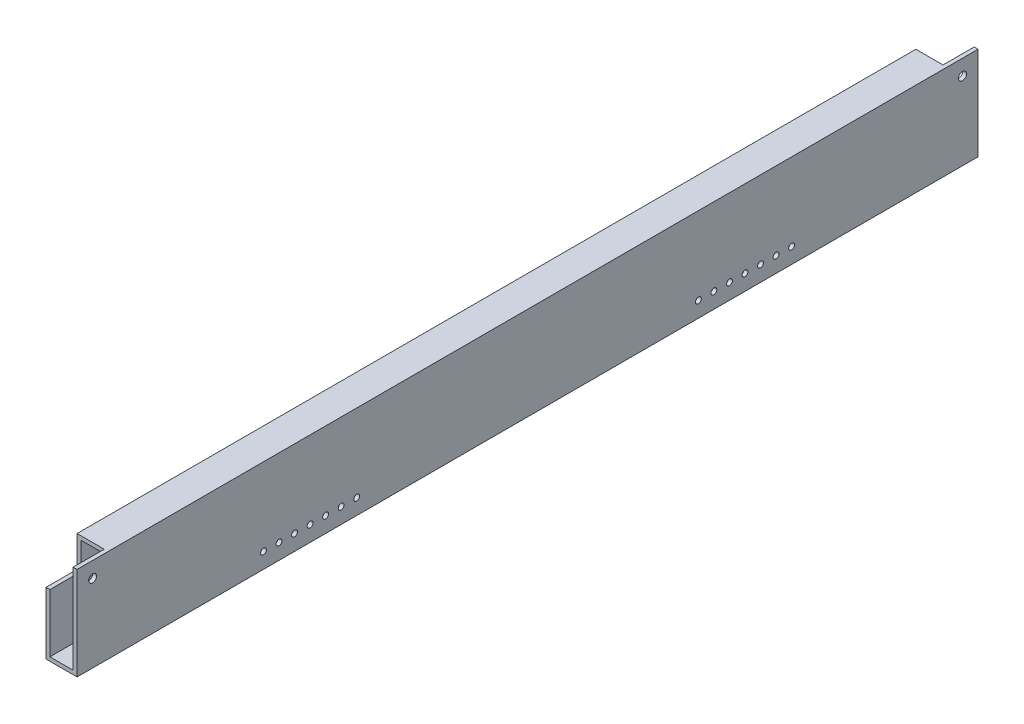
SolidWorks part; units mm, degrees
ref_plane "Front Plane" through (0, 0, 0) normal (0, 0, 1) x (1, 0, 0)
ref_plane "Top Plane" through (0, 0, 0) normal (0, 1, 0) x (1, 0, 0)
ref_plane "Right Plane" through (0, 0, 0) normal (1, 0, 0) x (0, 0, -1)
sketch "Sketch1" plane through (0, 0, 0) normal (0, 0, 1) x (1, 0, 0)
  line L1 (-12.7, -38.1) -> (12.7, -38.1)
  line L2 (-12.7, -38.1) -> (-12.7, 38.1)
  line L3 (-12.7, 38.1) -> (12.7, 38.1)
  line L4 (12.7, -38.1) -> (12.7, 38.1)
  line L5 (-12.7, -38.1) -> (12.7, 38.1) construction
  line L6 (-12.7, 38.1) -> (12.7, -38.1) construction
  point P0 (0, 0)
  dimension "D1" = 25.4
  dimension "D2" = 76.2
extrude "Boss-Extrude1" add sketch "Sketch1" along normal mid plane 736.6
shell "Shell1" thickness 3.175 removed face at (0, 0, -368.3) removed face at (0, 0, 368.3)
sketch "Sketch3" plane through (12.7, 0, 0) normal (1, 0, 0) x (0, 0, -1)
  line L0 (368.3, -38.1) -> (368.3, 38.1) construction
  line L1 (-368.3, -38.1) -> (368.3, -38.1) construction
  line L2 (0, -53.276) -> (0, 47.534) construction
  circle A0 centre (215.9, -25.4) radius 2.3813
  circle A1 centre (203.2, -25.4) radius 2.3813
  circle A2 centre (190.5, -25.4) radius 2.3813
  circle A3 centre (177.8, -25.4) radius 2.3813
  circle A4 centre (165.1, -25.4) radius 2.3813
  circle A5 centre (152.4, -25.4) radius 2.3813
  circle A6 centre (139.7, -25.4) radius 2.3813
  circle A7 centre (-139.7, -25.4) radius 2.3813
  circle A8 centre (-152.4, -25.4) radius 2.3813
  circle A9 centre (-165.1, -25.4) radius 2.3813
  circle A10 centre (-203.2, -25.4) radius 2.3813
  circle A11 centre (-177.8, -25.4) radius 2.3813
  circle A12 centre (-215.9, -25.4) radius 2.3813
  circle A13 centre (-190.5, -25.4) radius 2.3813
  dimension "D1" = 4.7625
  dimension "D3" = 12.7
  dimension "D4" = 12.7
  dimension "D5" = 12.7
  dimension "D6" = 12.7
  dimension "D7" = 12.7
  dimension "D8" = 12.7
  dimension "D9" = 12.7
  dimension "D10" = 12.7
  dimension "D2" = 152.4
extrude "Cut-Extrude2" cut sketch "Sketch3" against normal up to next
sketch "Sketch4" plane through (-12.7, 0, 0) normal (-1, 0, 0) x (0, 0, 1)
  line L1 (-368.3, 38.1) -> (-342.9, 38.1)
  line L2 (-368.3, 38.1) -> (-368.3, 12.7)
  line L3 (-368.3, 12.7) -> (-342.9, 12.7)
  line L4 (-342.9, 38.1) -> (-342.9, 12.7)
  line L5 (368.3, 38.1) -> (342.9, 38.1)
  line L6 (368.3, 38.1) -> (368.3, 12.7)
  line L7 (368.3, 12.7) -> (342.9, 12.7)
  line L8 (342.9, 38.1) -> (342.9, 12.7)
  dimension "D1" = 25.4
  dimension "D2" = 25.4
  dimension "D3" = 25.4
  dimension "D4" = 25.4
extrude "Cut-Extrude3" cut sketch "Sketch4" against normal blind 22.225
sketch "Sketch5" plane through (9.525, 0, 0) normal (-1, 0, 0) x (0, 0, 1)
  line L0 (-342.9, 38.1) -> (-368.3, 38.1) construction
  line L1 (-368.3, -34.925) -> (-368.3, 38.1) construction
  line L2 (368.3, 38.1) -> (342.9, 38.1) construction
  line L4 (368.3, -34.925) -> (368.3, 38.1) construction
  circle A0 centre (-355.6, 25.4) radius 3.25
  circle A1 centre (355.6, 25.4) radius 3.25
  dimension "D3" = 6.5
  dimension "D4" = 6.5
  dimension "D6" = 12.7
  dimension "D1" = 12.7
  dimension "D2" = 12.7
  dimension "D5" = 12.7
extrude "Cut-Extrude4" cut sketch "Sketch5" against normal blind 22.225
equation "\"robotwidth\"= 29in"
equation "\"D1@Boss-Extrude1\"=\"robotwidth\""
